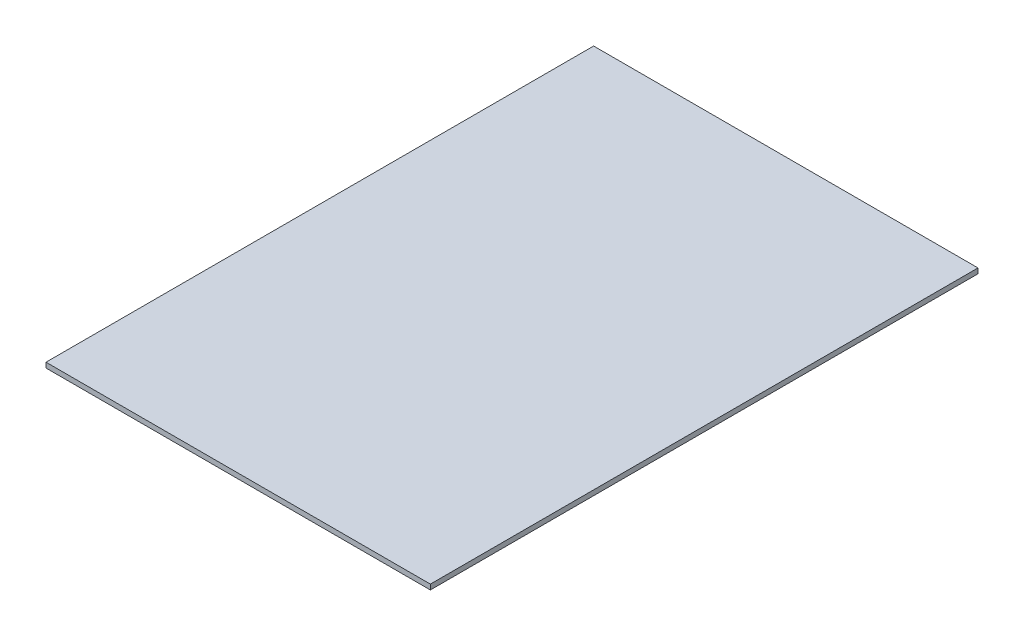
SolidWorks part; units mm, degrees
material "Zoltek Panex 33"
ref_plane "Front Plane" through (0, 0, 0) normal (0, 0, 1) x (1, 0, 0)
ref_plane "Top Plane" through (0, 0, 0) normal (0, 1, 0) x (1, 0, 0)
ref_plane "Right Plane" through (0, 0, 0) normal (1, 0, 0) x (0, 0, -1)
sketch "Sketch1" plane through (0, 0, 0) normal (0, 1, 0) x (1, 0, 0)
  line L1 (0, 0) -> (150.9, 0)
  line L2 (0, 0) -> (0, 215)
  line L3 (0, 215) -> (150.9, 215)
  line L4 (150.9, 0) -> (150.9, 215)
  dimension "D1" = 150.9
  dimension "D2" = 215
extrude "Boss-Extrude1" add sketch "Sketch1" along normal blind 2
